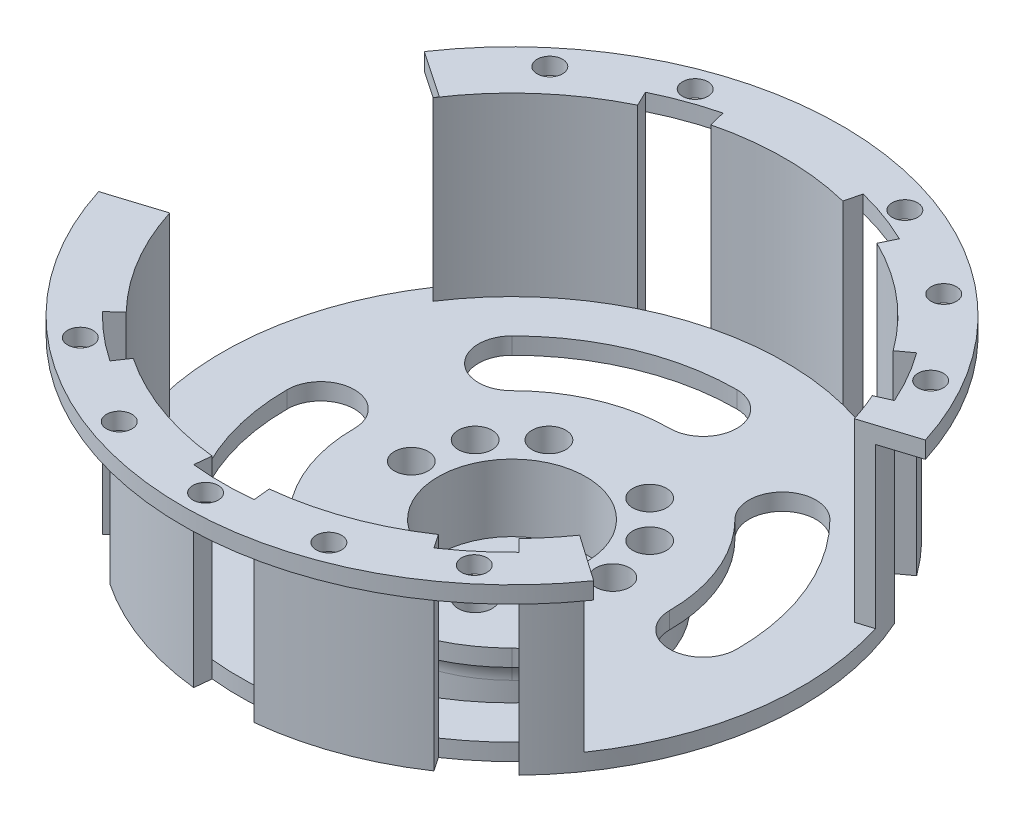
SolidWorks part; units mm, degrees
material "商用纯 CP-Ti UNS R50700 等级4 (SS)"
ref_plane "前视基准面" through (0, 0, 0) normal (0, 0, 1) x (1, 0, 0)
ref_plane "上视基准面" through (0, 0, 0) normal (0, 1, 0) x (1, 0, 0)
ref_plane "右视基准面" through (0, 0, 0) normal (1, 0, 0) x (0, 0, -1)
sketch "草图1" plane through (0, 0, 0) normal (0, 0, 1) x (1, 0, 0)
  line L0 (0, 79.6867) -> (0, -79.6867) construction
  line L1 (0, 25) -> (0, -25)
  line L2 (0, 25) -> (39.25, 25)
  line L3 (0, -25) -> (15, -25)
  line L4 (39.25, 25) -> (39.25, 7)
  line L7 (39.25, -22) -> (39.25, 7)
  line L8 (36.25, -25) -> (15, -25)
  arc A1 (36.25, -25) -> (39.25, -22) centre (36.25, -22) ccw
  point P4 (0, 0)
  point P8 (0, 0)
  dimension "D1" = 3
revolve "旋转1" add sketch "草图1" angle 360 about L0
sketch3d "3D草图1"
  point P0 (1.4057, -25, 0.4351)
ref_plane "基准面4" through (0, -25, 0) normal (0, -1, 0) x (1, 0, 0)
sketch "草图2" plane through (0, -25, 0) normal (0, -1, 0) x (1, 0, 0)
  circle A0 centre (0, 0) radius 15
sketch "草图3" plane through (0, -25, 0) normal (0, -1, 0) x (1, 0, 0)
  line L0 (0, -12) -> (0, 12) construction
  line L1 (0, 0) -> (6, 10.3923) construction
  line L2 (0, 0) -> (-6, 10.3923) construction
  line L3 (0, 0) -> (0, 39.25) construction
  line L5 (12.4837, 34.2988) -> (0, 0) construction
  circle A0 centre (0, 0) radius 12 construction
  circle A1 centre (0, 12) radius 2.015
  circle A2 centre (-6, 10.3923) radius 2.015
  circle A3 centre (6, 10.3923) radius 2.015
  circle A4 centre (12, 0) radius 2.015
  circle A5 centre (10.3923, -6) radius 2.015
  circle A6 centre (6, -10.3923) radius 2.015
  circle A7 centre (-6, -10.3923) radius 2.015
  circle A8 centre (-10.3923, -6) radius 2.015
  circle A9 centre (-12, 0) radius 2.015
  circle A10 centre (-12.4837, 34.2988) radius 1.515
  circle A11 centre (0, 0) radius 36.5 construction
  circle A12 centre (0, 36.5) radius 1.515
  circle A13 centre (23.4617, 27.9606) radius 1.515
  circle A14 centre (-23.4617, 27.9606) radius 1.515
  circle A15 centre (12.4837, 34.2988) radius 1.515
  circle A16 centre (35.9455, 6.3382) radius 1.515
  circle A17 centre (31.6099, -18.25) radius 1.515
  circle A18 centre (23.4617, -27.9606) radius 1.515
  circle A19 centre (12.4837, -34.2988) radius 1.515
  circle A20 centre (-12.4837, -34.2988) radius 1.515
  circle A21 centre (-31.6099, -18.25) radius 1.515
  circle A22 centre (-35.9455, -6.3382) radius 1.515
  circle A23 centre (-35.9455, 6.3382) radius 1.515
  circle A24 centre (-23.4617, -27.9606) radius 1.515
  circle A25 centre (35.9455, -6.3382) radius 1.515
  point P6 (0, 0)
  point P25 (0, 0)
  point P34 (0, 0)
  point P54 (0, 0)
  point P61 (0, 0)
  dimension "D1" = 3
  dimension "D2" = 2
  dimension "D3" = 3
  dimension "D10" = 4.03
  dimension "D11" = 4.03
  dimension "D4" = 2
extrude "切除-拉伸1" cut sketch "草图3" against normal blind 55
sketch3d "3D草图2"
  point P0 (-19.3365, 25, -23.4615)
ref_plane "基准面5" through (0, 25, 0) normal (0, 1, 0) x (1, 0, 0)
sketch "草图4" plane through (0, 25, 0) normal (0, 1, 0) x (1, 0, 0)
  circle A0 centre (0, 0) radius 32.5
extrude "切除-拉伸2" cut sketch "草图4" against normal blind 21
sketch3d "3D草图3"
  point P0 (0.2678, -25, 3.6481)
ref_plane "基准面6" through (0, -25, 0) normal (0, -1, 0) x (1, 0, 0)
sketch3d "3D草图4"
  point P0 (3.7222, 4, 0.375)
ref_plane "基准面7" through (0, 4, 0) normal (0, 1, 0) x (1, 0, 0)
sketch "草图6" plane through (0, 4, 0) normal (0, 1, 0) x (1, 0, 0)
  circle A0 centre (0, 0) radius 15
sketch3d "3D草图5"
  point P0 (30.0552, 25, 24.399)
ref_plane "基准面8" through (0, 25, 0) normal (0, 1, 0) x (-1, 0, 0)
sketch "草图7" plane through (0, 25, 0) normal (0, 1, 0) x (-1, 0, 0)
  circle A0 centre (23.4617, 27.9606) radius 1.5
  circle A1 centre (35.9455, 6.3382) radius 1.5
  circle A2 centre (-31.6099, -18.25) radius 1.5
sketch3d "3D草图6"
  point P0 (88.3921, 25, -23.5)
ref_plane "基准面9" through (0, 25, 0) normal (0, 1, 0) x (-0.9956, 0, 0.0941)
sketch "草图9" plane through (0, 25, 0) normal (0, 1, 0) x (-0.9956, 0, 0.0941)
  line L0 (0, 0) -> (-29.9579, 25.4144) construction
  line L1 (0, 0) -> (-38.4123, -8.2376) construction
  line L4 (0, 0) -> (38.4123, 8.2376) construction
  line L5 (0, 0) -> (30.2933, -25.0137) construction
  line L8 (-29.9579, 25.4144) -> (-24.7833, 21.0247)
  line L9 (-38.4123, -8.2376) -> (-31.7775, -6.8148)
  line L10 (31.5533, 6.7667) -> (38.4123, 8.2376)
  line L11 (25.0678, -20.6989) -> (30.2933, -25.0137)
  arc A0 (-29.9579, 25.4144) -> (-38.4123, -8.2376) centre (0, 0) ccw
  circle A1 centre (0, 0) radius 39.2857 construction
  circle A2 centre (0, 0) radius 32.509 construction
  arc A4 (38.4123, 8.2376) -> (30.2933, -25.0137) centre (0, 0) cw
  arc A6 (-24.7833, 21.0247) -> (-31.7775, -6.8148) centre (0, 0) ccw
  circle A7 centre (0, 0) radius 32.5 construction
  arc A8 (31.5533, 6.7667) -> (25.0678, -20.6989) centre (-0.7227, -0.1104) cw
extrude "切除-拉伸5" cut sketch "草图9" against normal blind 21
sketch3d "3D草图7"
  point P0 (-2.114, -25, 2.0207)
ref_plane "基准面10" through (0, -25, 0) normal (0, -1, 0) x (1, 0, 0)
ref_plane "基准面11" through (0, 35, 0) normal (0, 1, 0) x (1, 0, 0)
sketch "草图11" plane through (0, 35, 0) normal (0, 1, 0) x (1, 0, 0)
  circle A0 centre (0, 0) radius 39.25
ref_plane "基准面12" through (0, -35, 0) normal (0, -1, 0) x (-1, 0, 0)
sketch "草图12" plane through (0, -35, 0) normal (0, -1, 0) x (-1, 0, 0)
  circle A0 centre (0, 0) radius 39.25
extrude "切除-拉伸8" cut sketch "草图12" against normal blind 37
fillet "圆角8" radius 3 1 edges at (0, 2, -39.25)
ref_plane "基准面13" through (0, -8, 0) normal (0, -1, 0) x (-1, 0, 0)
ref_plane "基准面14" through (0, 25, 0) normal (0, 1, 0) x (1, 0, 0)
sketch "草图13" plane through (0, 25, 0) normal (0, 1, 0) x (1, 0, 0)
  circle A0 centre (0, 0) radius 34.5 construction
sketch "草图14" plane through (0, -8, 0) normal (0, -1, 0) x (-1, 0, 0)
  circle A0 centre (0, 0) radius 34.5
  circle A1 centre (0, 0) radius 39.4921
extrude "切除-拉伸9" cut sketch "草图14" against normal blind 31
ref_plane "基准面16" through (0, 2, 0) normal (0, -1, 0) x (-1, 0, 0)
sketch "草图16" plane through (0, 2, 0) normal (0, -1, 0) x (-1, 0, 0)
  line L1 (-22.7728, 22.7728) -> (22.7728, 22.7728) construction
  line L2 (-22.7728, 22.7728) -> (-22.7728, -22.7728) construction
  line L3 (-22.7728, -22.7728) -> (22.7728, -22.7728) construction
  line L4 (22.7728, 22.7728) -> (22.7728, -22.7728) construction
  line L5 (0, -22.7728) -> (0, 22.7728) construction
  line L6 (-22.7728, 0) -> (22.7728, 0) construction
  circle A0 centre (0, 0) radius 22.7728 construction
  arc A1 (0, 22.7728) -> (16.1028, 16.1028) centre (0, 0) cw construction
  arc A2 (18.9312, 18.9312) -> (0, 26.7728) centre (0, 0) ccw
  arc A3 (13.2743, 13.2743) -> (0, 18.7728) centre (0, 0) ccw
  arc A4 (13.2743, 13.2743) -> (18.9312, 18.9312) centre (16.1028, 16.1028) ccw
  arc A5 (0, 26.7728) -> (0, 18.7728) centre (0, 22.7728) ccw
  arc A6 (22.7728, 0) -> (16.1028, -16.1028) centre (0, 0) cw construction
  arc A7 (18.9312, -18.9312) -> (26.7728, 0) centre (0, 0) ccw
  arc A8 (13.2743, -13.2743) -> (18.7728, 0) centre (0, 0) ccw
  arc A9 (13.2743, -13.2743) -> (18.9312, -18.9312) centre (16.1028, -16.1028) ccw
  arc A10 (26.7728, 0) -> (18.7728, 0) centre (22.7728, 0) ccw
  arc A11 (0, -22.7728) -> (-16.1028, -16.1028) centre (0, 0) cw construction
  arc A12 (-18.9312, -18.9312) -> (0, -26.7728) centre (0, 0) ccw
  arc A13 (-13.2743, -13.2743) -> (0, -18.7728) centre (0, 0) ccw
  arc A14 (-13.2743, -13.2743) -> (-18.9312, -18.9312) centre (-16.1028, -16.1028) ccw
  arc A15 (0, -26.7728) -> (0, -18.7728) centre (0, -22.7728) ccw
  arc A16 (-22.7728, 0) -> (-16.1028, 16.1028) centre (0, 0) cw construction
  arc A17 (-18.9312, 18.9312) -> (-26.7728, 0) centre (0, 0) ccw
  arc A18 (-13.2743, 13.2743) -> (-18.7728, 0) centre (0, 0) ccw
  arc A19 (-13.2743, 13.2743) -> (-18.9312, 18.9312) centre (-16.1028, 16.1028) ccw
  arc A20 (-26.7728, 0) -> (-18.7728, 0) centre (-22.7728, 0) ccw
  point P7 (8.7148, 21.0393)
  point P16 (21.0393, -8.7148)
  point P23 (-8.7148, -21.0393)
  point P30 (-21.0393, 8.7148)
  point P36 (0, 0)
  dimension "D1" = 4
extrude "切除-拉伸10" cut sketch "草图16" against normal blind 25
sketch3d "3D草图8"
  point P0 (15.4023, 2, -1.5743)
ref_plane "基准面17" through (0, 2, 0) normal (0, -1, 0) x (1, 0, 0)
sketch "草图17" plane through (0, 2, 0) normal (0, -1, 0) x (1, 0, 0)
  circle A0 centre (0, 0) radius 15
extrude "凸台-拉伸1" add sketch "草图17" along normal blind 7
sketch3d "3D草图9"
  point P0 (4.7504, 4, -1.6413)
ref_plane "基准面18" through (0, 4, 0) normal (0, 1, 0) x (1, 0, 0)
sketch "草图18" plane through (0, 4, 0) normal (0, 1, 0) x (1, 0, 0)
  circle A0 centre (-6, 10.3923) radius 2.015
  circle A1 centre (-10.3923, 6) radius 2.015
  circle A2 centre (-12, 0) radius 2.015
  circle A3 centre (0, 0) radius 12 construction
  circle A4 centre (12, 0) radius 2.015
  circle A5 centre (10.3923, 6) radius 2.015
  circle A6 centre (6, 10.3923) radius 2.015
  circle A7 centre (-6, -10.3923) radius 2.015
  circle A8 centre (0, -12) radius 2.015
  circle A9 centre (6, -10.3923) radius 2.015
  point P26 (0, 0)
  dimension "D2" = 4.03
  dimension "D3" = 4.03
  dimension "D4" = 4.03
  dimension "D1" = 3
extrude "切除-拉伸11" cut sketch "草图18" against normal blind 21
fillet "圆角9" radius 4 1 edges at (0, 2, -15)
sketch3d "3D草图10"
  point P0 (0.2618, -5, 2.3783)
ref_plane "基准面19" through (0, -5, 0) normal (0, -1, 0) x (1, 0, 0)
sketch "草图19" plane through (0, -5, 0) normal (0, -1, 0) x (1, 0, 0)
  circle A0 centre (0, 0) radius 6
extrude "切除-拉伸12" cut sketch "草图19" against normal blind 21
ref_plane "基准面21" through (0, 2, 0) normal (0, -1, 0) x (-1, 0, 0)
ref_plane "基准面22" through (0, 2, 0) normal (0, -1, 0) x (-1, 0, 0)
sketch "草图22" plane through (0, 2, 0) normal (0, -1, 0) x (-1, 0, 0)
  line L0 (0, 0) -> (-31.6099, 18.25) construction
  line L1 (0, 0) -> (-33.3444, 14.8459) construction
  line L2 (0, 0) -> (-29.5291, 21.4542) construction
  line L3 (-27.9111, 20.2786) -> (-26.2931, 19.103)
  line L4 (-29.6902, 13.2189) -> (-31.5173, 14.0324)
  line L5 (0, 0) -> (-23.4617, 27.9606) construction
  line L6 (-15.1238, 31.0084) -> (-14.2471, 29.2108)
  line L7 (-7.8625, 31.5346) -> (-8.3463, 33.4752)
  line L12 (-23.3785, -22.5764) -> (-24.8172, -23.9657)
  line L13 (-19.2922, -28.6018) -> (-18.1738, -26.9437)
  line L14 (3.3972, -32.322) -> (3.6062, -34.311)
  line L15 (-3.6062, -34.311) -> (-3.3972, -32.322)
  line L16 (26.2931, 19.103) -> (27.9111, 20.2786) [skipped]
  line L17 (31.5173, 14.0324) -> (29.6902, 13.2189) [skipped]
  line L18 (31.241, -8.9582) -> (33.1635, -9.5095) [skipped]
  line L19 (34.416, -2.4066) -> (32.4208, -2.2671) [skipped]
  line L20 (14.2471, 29.2108) -> (15.1238, 31.0084)
  line L21 (8.3463, 33.4752) -> (7.8625, 31.5346)
  line L22 (23.3785, -22.5764) -> (24.8172, -23.9657)
  line L23 (19.2922, -28.6018) -> (18.1738, -26.9437)
  circle A0 centre (0, 0) radius 34.5 construction
  circle A1 centre (0, 0) radius 32.5 construction
  arc A2 (-27.9111, 20.2786) -> (-31.5173, 14.0324) centre (0, 0) ccw
  arc A3 (-26.2931, 19.103) -> (-29.6902, 13.2189) centre (0, 0) ccw
  arc A4 (-14.2471, 29.2108) -> (-7.8625, 31.5346) centre (0, 0) cw
  arc A5 (-15.1238, 31.0084) -> (-8.3463, 33.4752) centre (0, 0) cw
  arc A10 (-18.1738, -26.9437) -> (-23.3785, -22.5764) centre (0, 0) cw
  arc A11 (-19.2922, -28.6018) -> (-24.8172, -23.9657) centre (0, 0) cw
  arc A12 (-3.6062, -34.311) -> (3.6062, -34.311) centre (0, 0) ccw
  arc A13 (-3.3972, -32.322) -> (3.3972, -32.322) centre (0, 0) ccw
  arc A14 (31.5173, 14.0324) -> (27.9111, 20.2786) centre (0, 0) ccw [skipped]
  arc A15 (29.6902, 13.2189) -> (26.2931, 19.103) centre (0, 0) ccw [skipped]
  arc A16 (34.416, -2.4066) -> (33.1635, -9.5095) centre (0, 0) cw [skipped]
  arc A17 (32.4208, -2.2671) -> (31.241, -8.9582) centre (0, 0) cw [skipped]
  arc A18 (7.8625, 31.5346) -> (14.2471, 29.2108) centre (0, 0) cw
  arc A19 (8.3463, 33.4752) -> (15.1238, 31.0084) centre (0, 0) cw
  arc A20 (19.2922, -28.6018) -> (24.8172, -23.9657) centre (0, 0) ccw
  arc A21 (18.1738, -26.9437) -> (23.3785, -22.5764) centre (0, 0) ccw
  point P27 (0, 0)
  point P39 (0, 0)
  point P42 (0, 0)
  dimension "D1" = 2
  dimension "D2" = 3
  dimension "D3" = 2
  dimension "D4" = 2
extrude "切除-拉伸14" cut sketch "草图22" against normal blind 29
ref_plane "基准面24" through (0, 4, 0) normal (0, 1, 0) x (1, 0, 0)
sketch "草图23" plane through (0, 4, 0) normal (0, 1, 0) x (1, 0, 0)
  circle A0 centre (0, 0) radius 8.8022
extrude "切除-拉伸16" cut sketch "草图23" against normal blind 8
